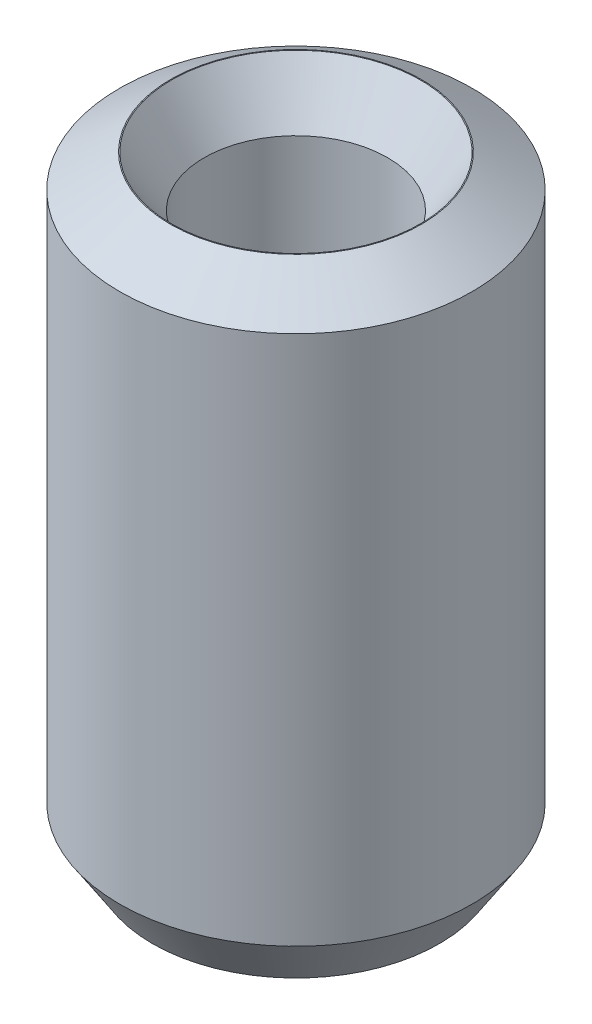
SolidWorks part; units mm, degrees
ref_plane "Front Plane" through (0, 0, 0) normal (0, 0, 1) x (1, 0, 0)
ref_plane "Top Plane" through (0, 0, 0) normal (0, 1, 0) x (1, 0, 0)
ref_plane "Right Plane" through (0, 0, 0) normal (1, 0, 0) x (0, 0, -1)
sketch "Sketch1" plane through (0, 0, 0) normal (0, 1, 0) x (1, 0, 0)
  circle A0 centre (0, 0) radius 12.5
  dimension "SLEEVE_OD" = 25
extrude "Boss-Extrude1" add sketch "Sketch1" along normal blind 43.5573
sketch "Sketch2" plane through (0, 0, 0) normal (0, 1, 0) x (1, 0, 0)
  circle A0 centre (0, 0) radius 6.5005
  dimension "BORE_D" = 13.0011
extrude "Cut-Extrude1" cut sketch "Sketch2" along normal through all
chamfer "Chamfer1" distance 2.3337 angle 57.046 4 edges at (0, 43.5573, 6.5005) (0, 0, 6.5005) (0, 0, 12.5) (0, 43.5573, 12.5) first distance on face at (0, 43.5573, 6.5005) first distance on face at (0, 0, 6.5005) first distance on face at (0, 43.5573, 12.5)
